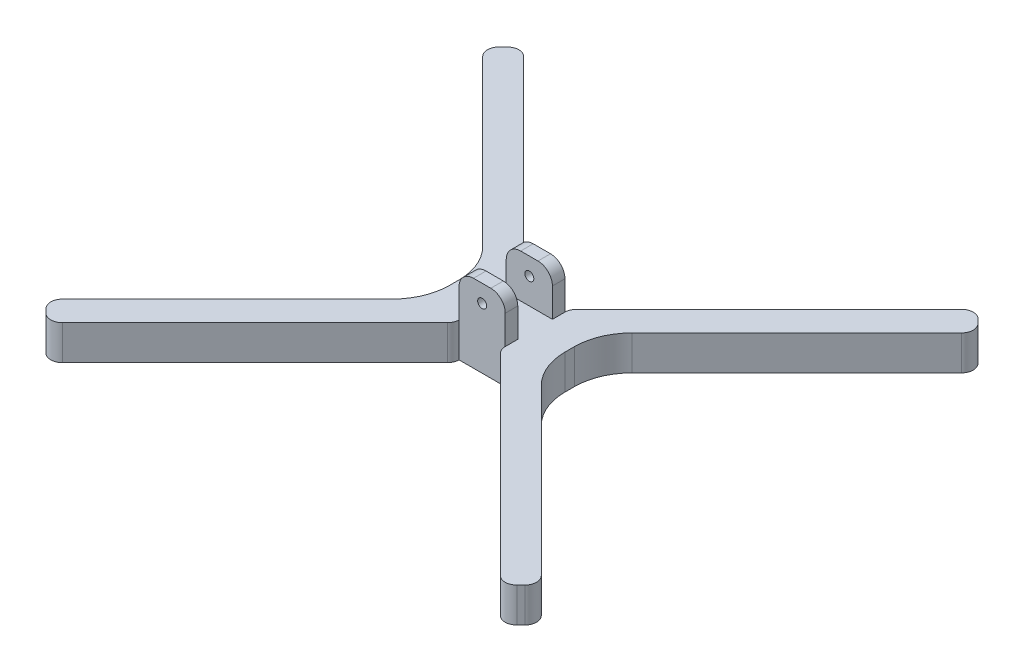
SolidWorks part; units mm, degrees
ref_plane "Front Plane" through (0, 0, 0) normal (0, 0, 1) x (1, 0, 0)
ref_plane "Top Plane" through (0, 0, 0) normal (0, 1, 0) x (1, 0, 0)
ref_plane "Right Plane" through (0, 0, 0) normal (1, 0, 0) x (0, 0, -1)
sketch "Sketch2" plane through (0, 0, 0) normal (0, 1, 0) x (1, 0, 0)
  line L1 (4, 6) -> (39.3553, 41.3553)
  line L2 (10, 4.9289) -> (42.8909, 37.8198)
  line L3 (39.3553, 41.3553) -> (42.8909, 37.8198)
  line L4 (0, -55) -> (0, 55) construction
  line L6 (-39.3553, 41.3553) -> (-42.8909, 37.8198)
  line L8 (-10, 4.9289) -> (-42.8909, 37.8198)
  line L9 (-4, 6) -> (-39.3553, 41.3553)
  line L10 (-55, 0) -> (55, 0) construction
  line L11 (39.3553, -41.3553) -> (42.8909, -37.8198)
  line L12 (10, -4.9289) -> (42.8909, -37.8198)
  line L13 (4, -6) -> (39.3553, -41.3553)
  line L16 (-10, -4.9289) -> (-42.8909, -37.8198)
  line L17 (-39.3553, -41.3553) -> (-42.8909, -37.8198)
  line L18 (-4, -6) -> (-39.3553, -41.3553)
  line L21 (-10, 4.9289) -> (-10, -4.9289)
  line L22 (10, 4.9289) -> (10, -4.9289)
  line L23 (-4, 6) -> (-4, 3)
  line L24 (-4, 3) -> (4, 3)
  line L25 (4, 6) -> (4, 3)
  line L26 (-4, -6) -> (-4, -3)
  line L27 (-4, -3) -> (4, -3)
  line L28 (4, -3) -> (4, -6)
  point P0 (0, 3)
  point P8 (-10, 0)
  point P18 (10, 0)
  point P25 (0, -3)
  dimension "D1" = 50
  dimension "D2" = 5
  dimension "D3" = 8
  dimension "D4" = 3
  dimension "D5" = 6
  dimension "D6" = 90
  dimension "D7" = 45
  dimension "D8" = 3
  dimension "D9" = 6
  dimension "D10" = 6
  dimension "D11" = 90
extrude "Boss-Extrude2" add sketch "Sketch2" along normal blind 6
fillet "Fillet1" radius 2 12 edges at (4, 3, -6) (4, 3, 6) (-4, 3, 6) (-4, 3, -6) (42.8909, 3, -37.8198) (39.3553, 3, -41.3553) (42.8909, 3, 37.8198) (39.3553, 3, 41.3553) (-39.3553, 3, 41.3553) (-42.8909, 3, 37.8198) (-39.3553, 3, -41.3553) (-42.8909, 3, -37.8198)
fillet "Fillet2" radius 10 4 edges at (-10, 3, 4.9289) (-10, 3, -4.9289) (10, 3, -4.9289) (10, 3, 4.9289)
scale "Echelle1" scale about centroid uniform scaling yes scale factor 2
sketch "Esquisse1" plane through (0, -3, 0) normal (0, -1, 0) x (1, 0, 0)
  line L0 (6.6, 0) -> (-6.6, 0) construction
  line L1 (-8, -6) -> (8, -6)
  line L2 (-8, -6) -> (-8, -10.3431)
  line L3 (-8, -10.3431) -> (8, -10.3431)
  line L4 (8, -6) -> (8, -10.3431)
  line L5 (8, 6) -> (8, 10.3431)
  line L6 (-8, 6) -> (8, 6)
  line L7 (-8, 6) -> (-8, 10.3431)
  line L8 (-8, 10.3431) -> (8, 10.3431)
extrude "Boss.-Extru.1" add sketch "Esquisse1" against normal offset from surface (27 mm away) 15 up to face at (0, 9, 0) offset beyond the face yes
sketch "Esquisse2" plane through (0, 0, -10.3431) normal (0, 0, -1) x (-1, 0, 0)
  line L0 (0, -3.175) -> (0, 49996.825) construction
  line L1 (8, -3) -> (-8, -3) construction
  circle A0 centre (0, 17.9559) radius 1.55
  point P6 (0, -3)
  dimension "D1" = 3.1
extrude "Enlèv. mat.-Extru.1" cut sketch "Esquisse2" against normal up to surface (20.6863 mm away) up to face at (0, 10, 10.3431)
fillet "Congé1" radius 5 4 edges at (8, 24, -8.1716) (-8, 24, -8.1716) (-8, 24, 8.1716) (8, 24, 8.1716)
equation "\"ScrewSize\"= 3.1mm"
